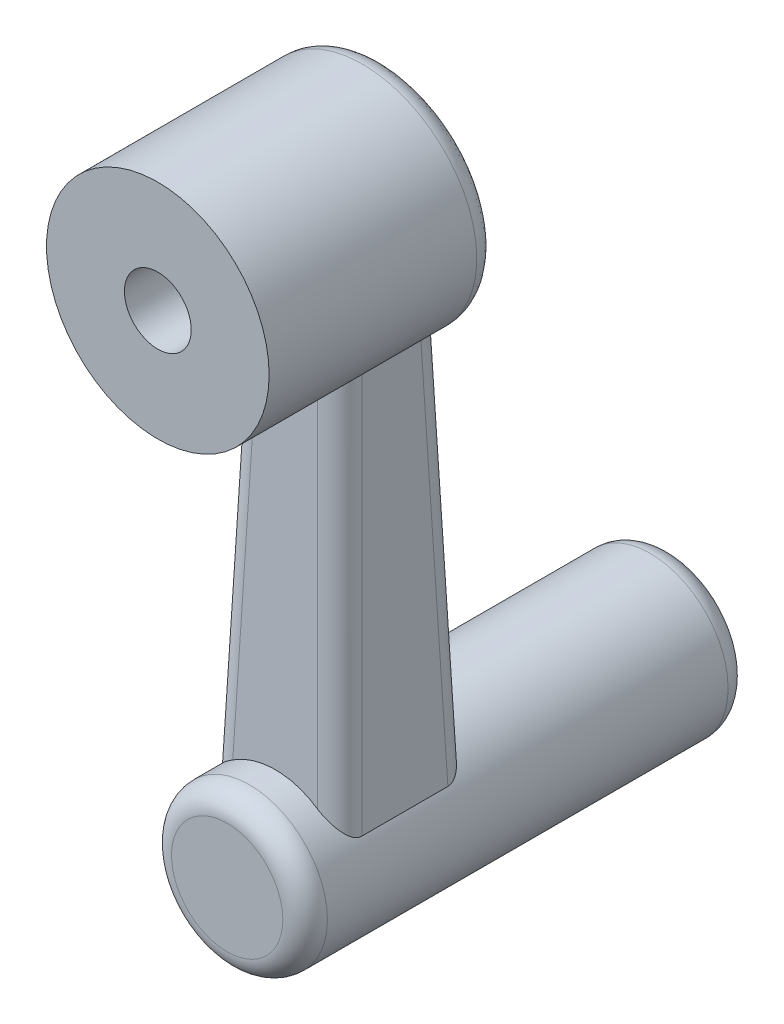
SolidWorks part; units mm, degrees
ref_plane "Front Plane" through (0, 0, 0) normal (0, 0, 1) x (1, 0, 0)
ref_plane "Top Plane" through (0, 0, 0) normal (0, 1, 0) x (1, 0, 0)
ref_plane "Right Plane" through (0, 0, 0) normal (1, 0, 0) x (0, 0, -1)
sketch "Sketch5" plane through (0, 0, 0) normal (0, 0, 1) x (1, 0, 0)
  circle A0 centre (0, 0) radius 17.5
  dimension "D1" = 35
extrude "Boss-Extrude1" add sketch "Sketch5" along normal blind 100
sketch "Sketch7" plane through (0, 0, 0) normal (0, 1, 0) x (1, 0, 0)
  line L0 (0, 0) -> (0, -100) construction
  line L1 (-17.5, -100) -> (17.5, -100) construction
sketch "Sketch8" plane through (0, 0, 0) normal (1, 0, 0) x (0, 0, -1)
  line L0 (-75, 17.5) -> (-75, -17.5) construction
  line L1 (0, 17.5) -> (-100, 17.5) construction
  line L2 (-100, -17.5) -> (0, -17.5) construction
  line L3 (-100, 17.5) -> (-100, -17.5) construction
  dimension "D1" = 25
sketch "Sketch9" plane through (0, 0, 0) normal (0, 1, 0) x (1, 0, 0)
  line L0 (0, 0) -> (0, -100) construction
  line L1 (-15, -59.7695) -> (15, -59.7695)
  line L2 (-15, -59.7695) -> (-15, -89.7695)
  line L3 (-15, -89.7695) -> (15, -89.7695)
  line L4 (15, -59.7695) -> (15, -89.7695)
  line L5 (-17.5, -74.7695) -> (30.6901, -74.7695) construction
  line L6 (-17.5, 0) -> (-17.5, -100) construction
  dimension "D1" = 15
  dimension "D2" = 30
  dimension "D3" = 15
  dimension "D4" = 30
extrude "Boss-Extrude2" add sketch "Sketch9" along normal blind 120 draft 2
ref_plane "Plane2" through (0, 0, 85.5791) normal (0, 0, 1) x (1, 0, 0)
sketch "Sketch13" plane through (0, 0, 85.5791) normal (0, 0, 1) x (1, 0, 0)
  line L0 (-10.8095, 120) -> (10.8095, 120) construction
  circle A0 centre (0, 120) radius 25
  dimension "D1" = 50
extrude "Boss-Extrude4" add sketch "Sketch13" along normal blind 30 and the other way up to surface other way up to face at (0, 66.7617, 62.1009)
sketch "Sketch14" plane through (0, 0, 115.5791) normal (0, 0, 1) x (1, 0, 0)
  circle A0 centre (0, 120) radius 7.5
  dimension "D1" = 15
extrude "Cut-Extrude1" cut sketch "Sketch14" against normal blind 25
fillet "Fillet1" radius 5 10 edges at (17.5, 0, 0) (13.1249, 53.696, 61.6447) (-13.1249, 53.696, 61.6447) (13.1249, 53.696, 87.8944) (-13.1249, 53.696, 87.8944) (0, 145, 64.8331) (0, 95, 86.4521) (17.5, 0, 100) (0, 17.5, 60.3807) (0, 17.5, 89.1584)
